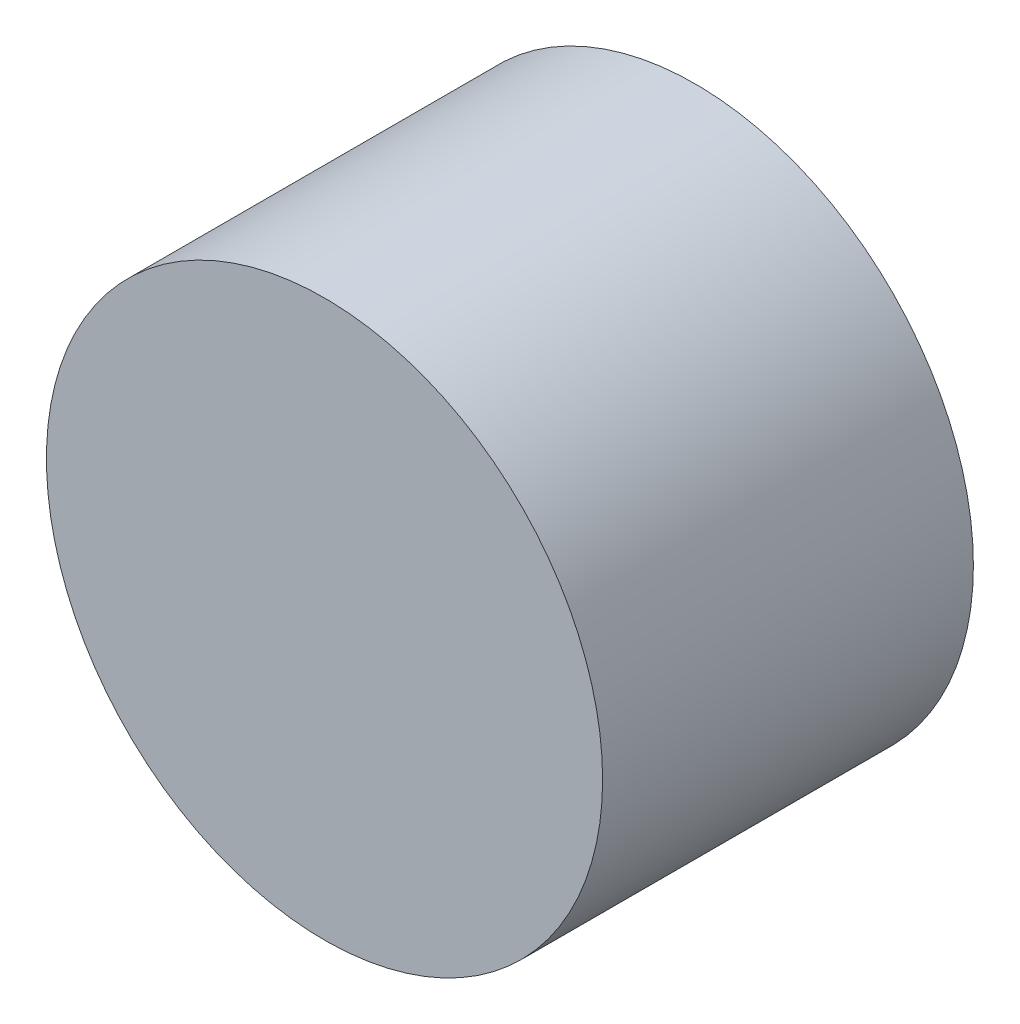
SolidWorks part; units mm, degrees
ref_plane "前视基准面" through (0, 0, 0) normal (0, 0, 1) x (1, 0, 0)
ref_plane "上视基准面" through (0, 0, 0) normal (0, 1, 0) x (1, 0, 0)
ref_plane "右视基准面" through (0, 0, 0) normal (1, 0, 0) x (0, 0, -1)
other "Configuration Table"
sketch "草图1" plane through (0, 0, 0) normal (0, 0, 1) x (1, 0, 0)
  circle A0 centre (0, 0) radius 18
extrude "凸台-拉伸1" add sketch "草图1" along normal mid plane 24
